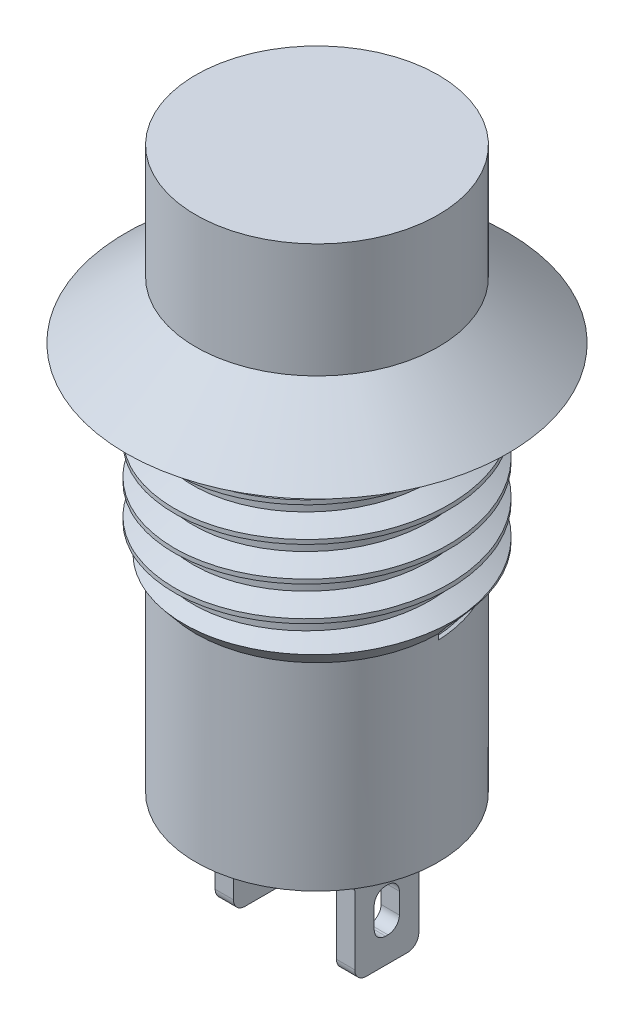
SolidWorks part; units mm, degrees
ref_plane "Front Plane" through (0, 0, 0) normal (0, 0, 1) x (1, 0, 0)
ref_plane "Top Plane" through (0, 0, 0) normal (0, 1, 0) x (1, 0, 0)
ref_plane "Right Plane" through (0, 0, 0) normal (1, 0, 0) x (0, 0, -1)
sketch "Sketch2" plane through (0, 0, 0) normal (1, 0, 0) x (0, 0, -1)
  line L0 (0, 0) -> (0, 34.2) construction
  line L1 (5.3, 19.5) -> (0, 19.5) construction
  line L2 (0, 0) -> (5.3, 0)
  line L3 (5.3, 0) -> (5.3, 8.646)
  line L4 (5.3, 8.646) -> (6, 9.5)
  line L5 (6, 9.5) -> (6, 17)
  line L6 (6, 17) -> (8.35, 17)
  line L7 (8.35, 17) -> (5.3, 19.5)
  line L8 (5.3, 19.5) -> (5.3, 24) construction
  line L9 (5.3, 24) -> (7, 24) construction
  line L10 (7, 24) -> (7, 31.9468) construction
  line L11 (0, 34.2) -> (-4.8228, 34.2) construction
  line L12 (0, 0) -> (0, 34.2) construction
  line L13 (0, 19.5) -> (0, 0)
  line L15 (0, 19.5) -> (5.3, 19.5) construction
  line L16 (0, 19.5) -> (0, 24.5)
  line L17 (0, 24.5) -> (5.3, 24.5)
  line L18 (5.3, 19.5) -> (5.3, 24.5)
  arc A0 (7, 31.9468) -> (0, 34.2) centre (0, 22.2) ccw construction
  dimension "D1" = 7
  dimension "D9" = 12
  dimension "D2" = 10.6
  dimension "D3" = 10.2
  dimension "D4" = 4.5
  dimension "D5" = 17
  dimension "D6" = 12
  dimension "D7" = 2.5
  dimension "D8" = 8.35
  dimension "D10" = 7.5
  dimension "D11" = 5.3
  dimension "D12" = 5
revolve "Revolve1" add sketch "Sketch2" angle 360 about L0
thread "Thread1" pitch 1.5 start angle 0, offset 0, length 9, pitch 1.5, diameter 12
ref_plane "Plane1" through (6, 17, 0) normal (0, 0, 1) x (1, 0, 0)
sketch "Thread Profile1" plane through (6, 17, 0) normal (0, 0, 1) x (1, 0, 0)
  line L0 (0, 0) -> (0, 1.5) construction
  line L11 (0, 0) -> (0, 1.3125)
  line L12 (0, 1.3125) -> (-0.8119, 0.8437)
  line L13 (-0.8119, 0.8437) -> (-0.8119, 0.4687)
  line L15 (-0.8119, 0.4687) -> (0, 0)
  line L17 (-0.8119, 0.6562) -> (0, 0.6562) construction
  point P2 (0, 0)
  dimension "Pitch" = 1.5
  dimension "Profile_Angle" = 60
  dimension "Profile_Land" = 0.375
  dimension "Profile_Height" = 0.8119
sketch "Sketch6" plane through (0, 0, 0) normal (0, -1, 0) x (1, 0, 0)
  line L0 (0, 0) -> (0, 14.0389) construction
  line L1 (0, 0) -> (-2.25, 0) construction
  line L2 (-3.05, -2.5) -> (-2.25, -2.5)
  line L3 (-3.05, -2.5) -> (-3.05, 2.5)
  line L4 (-3.05, 2.5) -> (-2.25, 2.5)
  line L5 (-2.25, -2.5) -> (-2.25, 2.5)
  line L6 (2.25, -2.5) -> (2.25, 2.5)
  line L7 (3.05, 2.5) -> (2.25, 2.5)
  line L8 (3.05, -2.5) -> (3.05, 2.5)
  line L9 (3.05, -2.5) -> (2.25, -2.5)
  dimension "D1" = 2.25
  dimension "D2" = 0.8
  dimension "D3" = 5
extrude "Boss-Extrude1" add sketch "Sketch6" along normal blind 5
sketch "Sketch7" plane through (3.05, 0, 0) normal (1, 0, 0) x (0, 0, -1)
  line L0 (-2.5, -1) -> (-1.4, -1)
  line L1 (-2.5, -5) -> (-2.5, 0) construction
  line L2 (-1.4, -1) -> (-1.4, -5)
  line L3 (2.5, -5) -> (-2.5, -5) construction
  line L4 (-1.4, -5) -> (1.4, -5) construction
  line L5 (-2.5, -1) -> (-2.5, -5)
  line L6 (-2.5, -5) -> (-1.4, -5)
  line L7 (2.5, 0) -> (-2.5, 0) construction
  line L8 (0, -5) -> (0, -0.5337) construction
  line L9 (0.55, -3.9) -> (-0.55, -3.9)
  line L10 (-0.55, -3.9) -> (-0.55, -2)
  line L11 (-0.55, -2) -> (0.55, -2)
  line L12 (0.55, -3.9) -> (0.55, -2)
  line L13 (2.5, -5) -> (1.4, -5)
  line L14 (2.5, -1) -> (2.5, -5)
  line L15 (1.4, -1) -> (1.4, -5)
  line L16 (2.5, -1) -> (1.4, -1)
  point P20 (0, -2)
  point P21 (0, -3.9)
  dimension "D1" = 1.4
  dimension "D2" = 1
  dimension "D3" = 0.55
  dimension "D4" = 1.9
  dimension "D5" = 1.1
extrude "Cut-Extrude1" cut sketch "Sketch7" against normal through all both and the other way through all
fillet "Fillet1" radius 0.5 20 edges at (2.65, -5, 1.4) (2.65, -5, -1.4) (2.65, -1, -1.4) (2.65, -1, -2.5) (2.65, -1, 1.4) (2.65, -1, 2.5) (-2.65, -5, 1.4) (-2.65, -5, -1.4) (-2.65, -1, -1.4) (-2.65, -1, 2.5) (-2.65, -1, 1.4) (-2.65, -1, -2.5) (-2.65, -3.9, -0.55) (-2.65, -3.9, 0.55) (-2.65, -2, 0.55) (2.65, -3.9, -0.55) (2.65, -3.9, 0.55) (2.65, -2, 0.55) (-2.65, -2, -0.55) (2.65, -2, -0.55)
